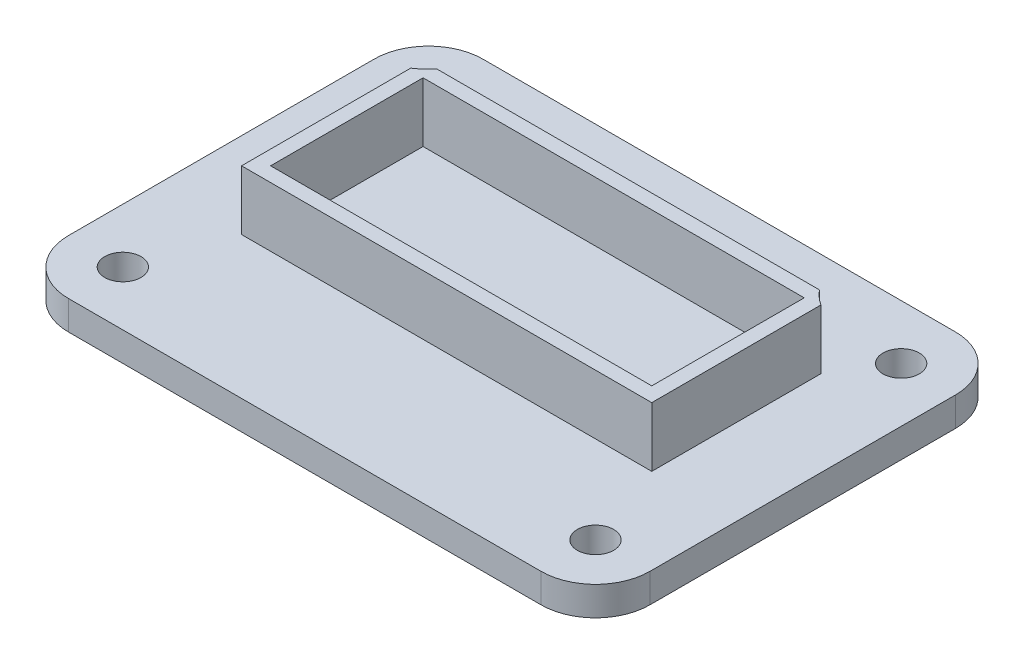
SolidWorks part; units mm, degrees
ref_plane "Спереди" through (0, 0, 0) normal (0, 0, 1) x (1, 0, 0)
ref_plane "Сверху" through (0, 0, 0) normal (0, 1, 0) x (1, 0, 0)
ref_plane "Справа" through (0, 0, 0) normal (1, 0, 0) x (0, 0, -1)
sketch "Эскиз1" plane through (0, 0, 0) normal (0, 1, 0) x (1, 0, 0)
  line L0 (-32.55, 56.4999) -> (-32.55, -14.6985) construction
  line L1 (0, 0) -> (-65.1, 0) construction
  line L2 (0, 0) -> (0, 42.1) construction
  line L3 (0, 42.1) -> (-65.1, 42.1) construction
  line L4 (-65.1, 0) -> (-65.1, 42.1) construction
  line L5 (-65.1, 49.6) -> (0, 49.6)
  line L6 (-72.6, 42.1) -> (-72.6, 0)
  line L7 (-65.1, -7.5) -> (0, -7.5)
  line L8 (7.5, 42.1) -> (7.5, 0)
  line L9 (-80.2533, 21.05) -> (15.1494, 21.05) construction
  line L10 (-62.8247, 24.55) -> (-2.2753, 24.55) construction
  line L11 (-60.8, 37.05) -> (-4.3, 37.05)
  line L12 (-60.8, 37.05) -> (-60.8, 12.05)
  line L13 (-60.8, 12.05) -> (-4.3, 12.05)
  line L14 (-4.3, 37.05) -> (-4.3, 12.05)
  line L15 (-32.55, 38.4292) -> (-32.55, 10.2742) construction
  line L16 (-58.8, 35.05) -> (-6.3, 35.05)
  line L17 (-58.8, 35.05) -> (-58.8, 14.05)
  line L18 (-58.8, 14.05) -> (-6.3, 14.05)
  line L19 (-6.3, 35.05) -> (-6.3, 14.05)
  line L20 (-65.1, 36.1) -> (-71.1, 36.1)
  line L21 (-59.1, 42.1) -> (-59.1, 48.1)
  line L22 (0, 36.1) -> (6, 36.1)
  line L23 (-6, 42.1) -> (-6, 48.1)
  line L24 (0, 6) -> (6, 6)
  line L25 (-6, 0) -> (-6, -6)
  line L26 (-65.1, 6) -> (-71.1, 6)
  line L27 (-59.1, 0) -> (-59.1, -6)
  line L28 (-55.6, 47.6) -> (-9.5, 47.6)
  line L29 (-57.1, 46.1) -> (-57.1, 42.1)
  line L30 (-65.1, 34.1) -> (-69.1, 34.1)
  line L31 (-70.6, 32.6) -> (-70.6, 9.5)
  line L32 (5.5, 32.6) -> (5.5, 9.5)
  line L33 (0, 34.1) -> (4, 34.1)
  line L34 (-8, 46.1) -> (-8, 42.1)
  line L35 (-65.1, 8) -> (-69.1, 8)
  line L36 (-57.1, -4) -> (-57.1, 0)
  line L37 (-55.6, -5.5) -> (-9.5, -5.5)
  line L38 (-8, -4) -> (-8, 0)
  line L39 (0, 8) -> (4, 8)
  circle A0 centre (-65.1, 42.1) radius 2.5
  arc A4 (-65.1, 49.6) -> (-72.6, 42.1) centre (-65.1, 42.1) ccw
  circle A5 centre (0, 42.1) radius 2.5
  circle A6 centre (0, 0) radius 2.5
  circle A7 centre (-65.1, 0) radius 2.5
  arc A8 (0, 49.6) -> (7.5, 42.1) centre (0, 42.1) cw
  arc A9 (0, -7.5) -> (7.5, 0) centre (0, 0) ccw
  arc A10 (-65.1, -7.5) -> (-72.6, 0) centre (-65.1, 0) cw
  circle A11 centre (0, 42.1) radius 6 construction
  circle A12 centre (-65.1, 42.1) radius 6 construction
  circle A13 centre (0, 0) radius 6 construction
  circle A14 centre (-65.1, 0) radius 6 construction
  arc A15 (-59.1, 42.1) -> (-65.1, 36.1) centre (-65.1, 42.1) cw
  arc A16 (-57.6, 49.6) -> (-59.1, 48.1) centre (-57.6, 48.1) ccw
  arc A17 (-71.1, 36.1) -> (-72.6, 34.6) centre (-71.1, 34.6) ccw
  arc A18 (6, 36.1) -> (7.5, 34.6) centre (6, 34.6) cw
  arc A19 (-6, 42.1) -> (0, 36.1) centre (0, 42.1) ccw
  arc A20 (-7.5, 49.6) -> (-6, 48.1) centre (-7.5, 48.1) cw
  arc A21 (6, 6) -> (7.5, 7.5) centre (6, 7.5) ccw
  arc A22 (-6, 0) -> (0, 6) centre (0, 0) cw
  arc A23 (-7.5, -7.5) -> (-6, -6) centre (-7.5, -6) ccw
  arc A24 (-71.1, 6) -> (-72.6, 7.5) centre (-71.1, 7.5) cw
  arc A25 (-59.1, 0) -> (-65.1, 6) centre (-65.1, 0) ccw
  arc A26 (-57.6, -7.5) -> (-59.1, -6) centre (-57.6, -6) cw
  arc A27 (-55.6, 47.6) -> (-57.1, 46.1) centre (-55.6, 46.1) ccw
  arc A28 (-57.1, 42.1) -> (-65.1, 34.1) centre (-65.1, 42.1) cw
  arc A29 (-69.1, 34.1) -> (-70.6, 32.6) centre (-69.1, 32.6) ccw
  arc A30 (4, 34.1) -> (5.5, 32.6) centre (4, 32.6) cw
  arc A31 (-8, 42.1) -> (0, 34.1) centre (0, 42.1) ccw
  arc A32 (-9.5, 47.6) -> (-8, 46.1) centre (-9.5, 46.1) cw
  arc A33 (-69.1, 8) -> (-70.6, 9.5) centre (-69.1, 9.5) cw
  arc A34 (-57.1, 0) -> (-65.1, 8) centre (-65.1, 0) ccw
  arc A35 (-55.6, -5.5) -> (-57.1, -4) centre (-55.6, -4) cw
  arc A36 (-9.5, -5.5) -> (-8, -4) centre (-9.5, -4) ccw
  arc A37 (-8, 0) -> (0, 8) centre (0, 0) cw
  arc A38 (4, 8) -> (5.5, 9.5) centre (4, 9.5) ccw
  point P9 (-58.8, 24.55)
  point P13 (0, 21.05)
  point P19 (-32.55, 42.1)
  point P36 (-32.55, 12.05)
  point P37 (-32.55, 14.05)
  point P38 (-4.3, 24.55)
  point P39 (-6.3, 24.55)
  point P41 (-32.55, 35.05)
  point P42 (-32.55, 37.05)
  point P43 (-60.8, 24.55)
  point P48 (-32.55, 24.55)
  point P83 (0, 0)
  point P86 (-8.4393, 47.1607)
  point P89 (-70.6, 21.05)
  point P91 (-32.55, 47.6)
  point P102 (-32.55, 47.6)
  point P104 (-70.6, 21.05)
  point P112 (-8.4393, -5.0607)
  point P120 (5.5, 21.05)
  dimension "D3" = 5
  dimension "D4" = 7.5
  dimension "D5" = 21
  dimension "D6" = 52.5
  dimension "D9" = 12
  dimension "D11" = 1.5
  dimension "D12" = 1.5
  dimension "D14" = 1.5
  dimension "D16" = 1.5
  dimension "D1" = 65.1
  dimension "D2" = 42.1
  dimension "D7" = 2
  dimension "D8" = 2
  dimension "D10" = 3.5
  dimension "D13" = 2
  dimension "D15" = 2
  dimension "D17" = 2
extrude "Бобышка-Вытянуть1" add sketch "Эскиз1" along normal blind 4 contours L6 A10 L7 A9 L8 A8 L5 A4
extrude "Вырез-Вытянуть1" cut sketch "Эскиз1<3>" along normal blind 5 contours A0 | A5 | A6 | A7 region at (-65.1, 0, -42.1)
sketch "Эскиз1<3>" plane through (0, 0, 0) normal (0, 1, 0) x (1, 0, 0) same geometry as "Эскиз1"
extrude "Бобышка-Вытянуть2" add sketch "Эскиз1<4>" along normal blind 12.2 contours A31 L11 A28 L12 L13 L14 L16 L19 L18 L17 region at (-32.55, 0, -36.4322)
sketch "Эскиз1<4>" plane through (0, 0, 0) normal (0, 1, 0) x (1, 0, 0) same geometry as "Эскиз1"
